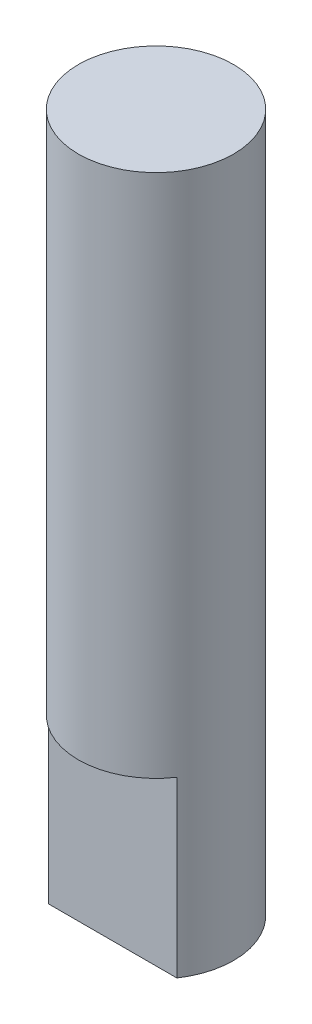
SolidWorks part; units mm, degrees
ref_plane "Front Plane" through (0, 0, 0) normal (0, 0, 1) x (1, 0, 0)
ref_plane "Top Plane" through (0, 0, 0) normal (0, 1, 0) x (1, 0, 0)
ref_plane "Right Plane" through (0, 0, 0) normal (1, 0, 0) x (0, 0, -1)
sketch "Sketch1" plane through (0, 0, 0) normal (0, 1, 0) x (1, 0, 0)
  circle A0 centre (0, 0) radius 3.175
  dimension "D1" = 6.35
extrude "Boss-Extrude1" add sketch "Sketch1" along normal blind 28.575
sketch "Sketch3" plane through (0, 0, 0) normal (0, -1, 0) x (1, 0, 0)
  line L0 (0, 0) -> (-2.6305, 1.778) construction
  line L1 (-2.6305, 1.778) -> (2.6305, 1.778)
  line L2 (2.6305, 1.778) -> (0, 0) construction
  line L3 (0, 0) -> (0, 1.778) construction
  line L4 (-2.6305, 1.778) -> (-3.6008, 3.8742)
  line L5 (-3.6008, 3.8742) -> (2.4914, 4.8441)
  line L6 (2.4914, 4.8441) -> (2.6305, 1.778)
  circle A0 centre (0, 0) radius 3.175 construction
  dimension "D1" = 1.778
extrude "Cut-Extrude2" cut sketch "Sketch3" against normal blind 7.112
